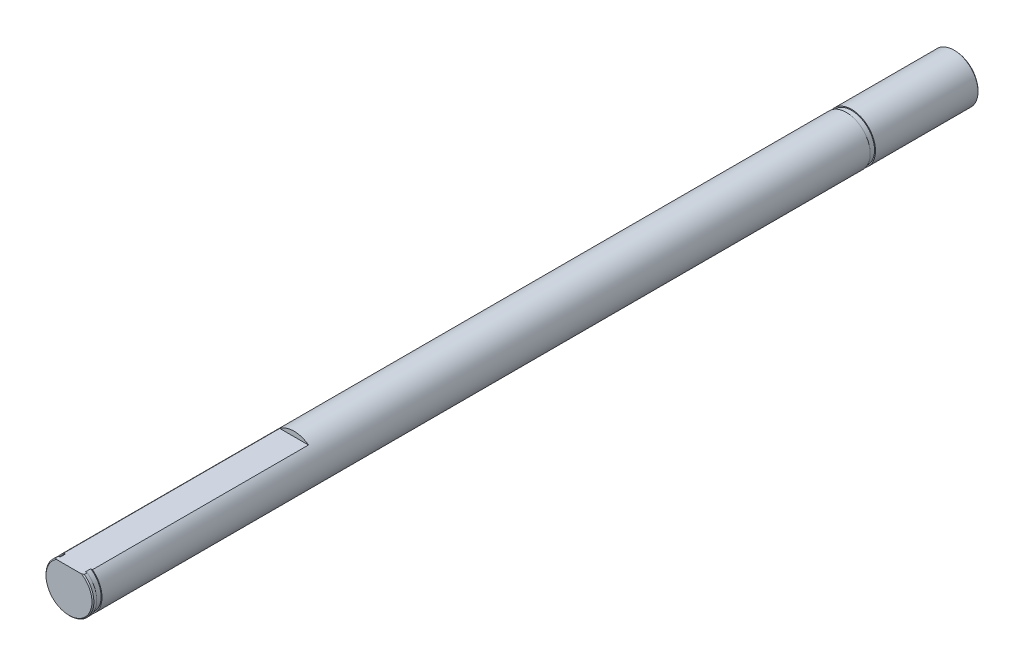
SolidWorks part; units mm, degrees
ref_plane "Vorne" through (0, 0, 0) normal (0, 0, 1) x (1, 0, 0)
ref_plane "Oben" through (0, 0, 0) normal (0, 1, 0) x (1, 0, 0)
ref_plane "Seite" through (0, 0, 0) normal (1, 0, 0) x (0, 0, -1)
sketch "Skizze1" plane through (0, 0, 0) normal (0, 0, 1) x (1, 0, 0)
  circle A0 centre (0, 0) radius 5
  point P3 (0, -3)
  dimension "D1" = 10
extrude "Aufsatz-Linear austragen1" add sketch "Skizze1" along normal mid plane 185
sketch "Skizze2" plane through (0, 0, 92.5) normal (0, 0, 1) x (1, 0, 0)
  point P0 (0, 0)
sketch "Skizze7" plane through (0, 0, 0) normal (1, 0, 0) x (0, 0, -1)
  line L0 (-91.7, 5) -> (-91.7, 4.8)
  line L1 (92.5, 5) -> (-92.5, 5) construction
  line L2 (-91.7, 4.8) -> (-90.6, 4.8)
  line L3 (-90.6, 4.8) -> (-90.6, 5)
  line L4 (-90.6, 5) -> (-91.7, 5)
  line L5 (70.9, 5) -> (70.9, 4.8)
  line L6 (70.9, 4.8) -> (69.8, 4.8)
  line L7 (69.8, 4.8) -> (69.8, 5)
  line L8 (69.8, 5) -> (70.9, 5)
  line L9 (-92.5, 5) -> (-92.5, -5) construction
  line L10 (92.5, 0) -> (-92.5, 0) construction
  line L11 (92.5, -5) -> (92.5, 5) construction
  dimension "D1" = 0.2
  dimension "D2" = 1.1
  dimension "D3" = 0.8
  dimension "D4" = 160.4
revolve "Schnitt-Rotation1" cut sketch "Skizze7" angle 360 about L10
sketch "Skizze8" plane through (0, 0, 92.5) normal (0, 0, 1) x (1, 0, 0)
  line L0 (3, 4) -> (-3, 4)
  line L1 (50, 0) -> (-50, 0) construction
  arc A0 (3, 4) -> (-3, 4) centre (0, 0) ccw
  circle A1 centre (0, 0) radius 5 construction
  dimension "D1" = 4
extrude "Schnitt-Linear austragen1" cut sketch "Skizze8" against normal blind 47
chamfer "Fase1" distance 0.2 angle 45 2 edges at (0, -5, 92.5) (5, 0, -92.5)
